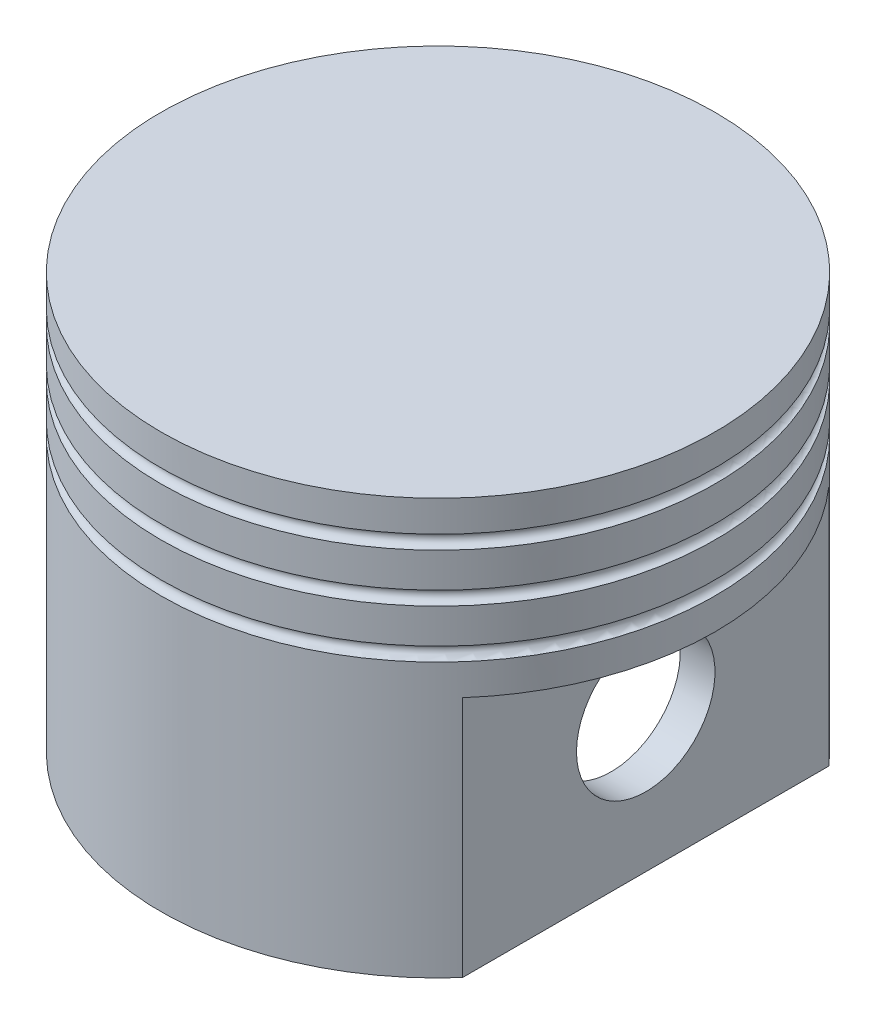
SolidWorks part; units mm, degrees
ref_plane "Front Plane" through (0, 0, 0) normal (0, 0, 1) x (1, 0, 0)
ref_plane "Top Plane" through (0, 0, 0) normal (0, 1, 0) x (1, 0, 0)
ref_plane "Right Plane" through (0, 0, 0) normal (1, 0, 0) x (0, 0, -1)
sketch "Sketch1" plane through (0, 0, 0) normal (0, 1, 0) x (1, 0, 0)
  circle A0 centre (0, 0) radius 40
  dimension "D1" = 80
extrude "Boss-Extrude1" add sketch "Sketch1" along normal blind 60
sketch "Sketch3" plane through (0, 0, 0) normal (0, -1, 0) x (1, 0, 0)
  line L0 (-30, 26.4575) -> (-30, -26.4575)
  line L1 (30, -26.4575) -> (30, 26.4575)
  arc A0 (30, -26.4575) -> (30, 26.4575) centre (0, 0) ccw
  circle A1 centre (0, 0) radius 40
  arc A2 (-30, 26.4575) -> (-30, -26.4575) centre (0, 0) ccw
  dimension "D1" = 0
  dimension "D2" = 60
extrude "Cut-Extrude1" cut sketch "Sketch3" against normal blind 35
sketch "Sketch4" plane through (0, 0, 0) normal (0, 0, 1) x (1, 0, 0)
  line L0 (-40, 60) -> (-40, 35) construction
  line L1 (0, 60) -> (0, 0) construction
  line L2 (40, 60) -> (-40, 60) construction
  circle A0 centre (-40, 54.5) radius 1
  circle A1 centre (-40, 47.5) radius 1
  circle A2 centre (-40, 40.5) radius 1
  dimension "D1" = 7
  dimension "D3" = 2
  dimension "D2" = 7
revolve "Cut-Revolve1" cut sketch "Sketch4" angle 360 about L1
shell "Shell1" thickness 5 removed face at (0, 0, 0)
sketch "Sketch5" plane through (-30, 0, 0) normal (-1, 0, 0) x (0, 0, 1)
  circle A0 centre (0, 20) radius 10
  dimension "D1" = 20
  dimension "D2" = 20
extrude "Cut-Extrude2" cut sketch "Sketch5" against normal through all
